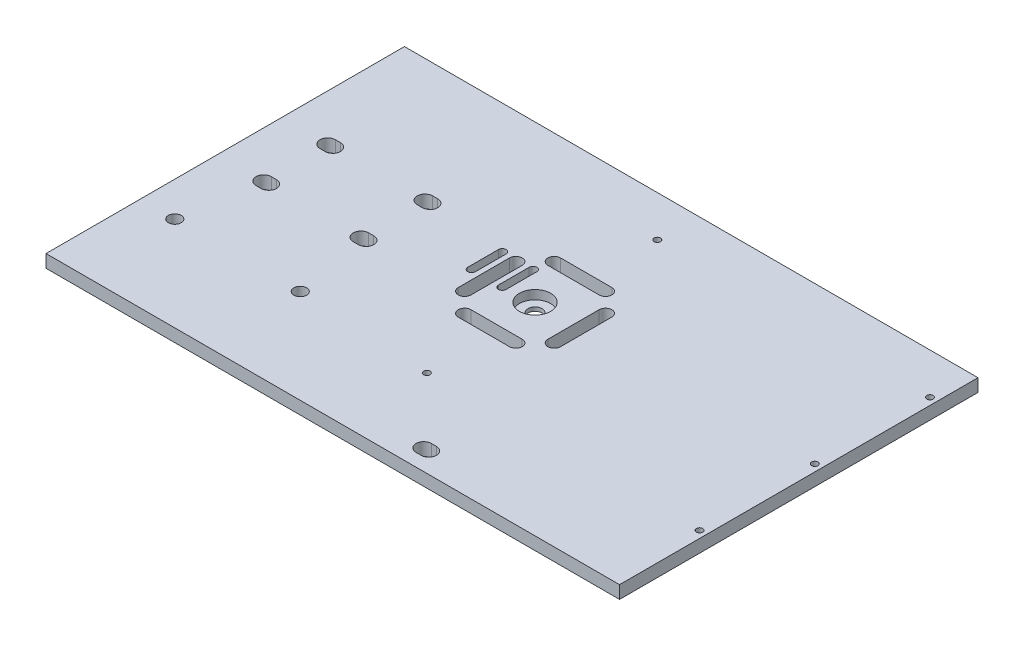
SolidWorks part; units mm, degrees
material "1060 Alloy"
ref_plane "Front Plane" through (0, 0, 0) normal (0, 0, 1) x (1, 0, 0)
ref_plane "Top Plane" through (0, 0, 0) normal (0, 1, 0) x (1, 0, 0)
ref_plane "Right Plane" through (0, 0, 0) normal (1, 0, 0) x (0, 0, -1)
sketch "Sketch1" plane through (0, 0, 0) normal (0, 1, 0) x (1, 0, 0)
  line L1 (-112, -61) -> (112, -61)
  line L2 (-112, -61) -> (-112, 61)
  line L3 (-112, 61) -> (112, 61)
  line L4 (112, -61) -> (112, 61)
  line L5 (-112, -61) -> (112, 61) construction
  line L6 (-112, 61) -> (112, -61) construction
  point P0 (0, 0)
  dimension "D1" = 122
  dimension "D2" = 224
extrude "Boss-Extrude1" add sketch "Sketch1" along normal blind 5
sketch "Sketch2" plane through (0, 0, 0) normal (0, -1, 0) x (1, 0, 0)
  line L0 (-17.5, 10) -> (-17.5, -10) construction
  line L1 (44.2539, 0) -> (-44.2539, 0) construction
  line L2 (-15, 10) -> (-15, -10)
  line L3 (-20, 10) -> (-20, -10)
  line L4 (0, -44.7868) -> (0, 44.7868) construction
  arc A0 (-15, 10) -> (-20, 10) centre (-17.5, 10) ccw
  arc A1 (-20, -10) -> (-15, -10) centre (-17.5, -10) ccw
  point P4 (-17.5, 0)
  dimension "D3" = 2.5
  dimension "D1" = 0
  dimension "D2" = 17.5
  dimension "D4" = 20
extrude "Cut-Extrude1" cut sketch "Sketch2" against normal blind 5
ref_axis "Axis1" through (0, -43.5149, 0) along (0, 1, 0)
pattern_circular "CirPattern1" count 4 over 360 about axis through (0, -43.5149, 0) along (0, 1, 0) of "Cut-Extrude1"
sketch "Sketch3" plane through (0, 0, 0) normal (0, 1, 0) x (1, 0, 0)
  circle A0 centre (0, 0) radius 2.75
  dimension "D1" = 5.5
extrude "Cut-Extrude5" cut sketch "Sketch3" along normal blind 5
hole_wizard "CBORE for M5 Hex Head Bolt1" positions "Sketch4" profile "Sketch6" counterbore size "M5" standard "ISO"
sketch "Sketch4" plane through (0, 5, 0) normal (0, 1, 0) x (1, 0, 0)
  point P0 (0, 0)
sketch "Sketch6" plane through (0, 5, 0) normal (1, 0, 0) x (0, 0, 1)
  line L0 (0, 0) -> (0, 14.0524)
  line L1 (0, 14.0524) -> (2.75, 12.4)
  line L2 (2.75, 12.4) -> (2.75, 3.5)
  line L3 (2.75, 3.5) -> (6.119, 3.5)
  line L4 (6.119, 3.5) -> (6.119, 0)
  line L5 (6.119, 0) -> (0, 0)
  line L10 (0, 14.0524) -> (-2.75, 12.4) construction
  line L11 (0, -6.35) -> (0, 107.95) construction
  dimension "Hole Dia." = 5.5
  dimension "Hole Depth" = 12.4
  dimension "C'Bore Dia." = 12.238
  dimension "C'Bore Depth" = 3.5
  dimension "Drill Angle" = 118
hole_wizard "Ø2.5mm Dowel Hole1" positions "Sketch9" profile "Sketch10" hole size "Ø2.5" standard "ISO"
sketch "Sketch9" plane through (0, 5, 0) normal (0, 1, 0) x (1, 0, 0)
  line L0 (-112, -61) -> (112, -61) construction
  line L1 (112, 61) -> (-112, 61) construction
  line L2 (112, -61) -> (112, 61) construction
  point P0 (109.25, -45)
  point P2 (109.25, 0)
  point P4 (109.25, 45)
  dimension "D1" = 16
  dimension "D2" = 16
  dimension "D3" = 2.75
  dimension "D4" = 0
  dimension "D5" = 0
sketch "Sketch10" plane through (109.25, 5, 45) normal (1, 0, 0) x (0, 0, 1)
  line L0 (0, 0) -> (0, 13.1511)
  line L1 (0, 13.1511) -> (1.25, 12.4)
  line L2 (1.25, 12.4) -> (1.25, 0)
  line L5 (1.25, 0) -> (0, 0)
  line L10 (0, 13.1511) -> (-1.25, 12.4) construction
  line L11 (0, -6.35) -> (0, 107.95) construction
  dimension "Hole Dia." = 2.5
  dimension "Hole Depth" = 12.4
  dimension "Drill Angle" = 118
ref_plane "Plane2" through (2.75, 0, 0) normal (1, 0, 0) x (0, 0, -1)
pattern_linear "LPattern1" count 2 spacing 106.5 along (-1, 0, 0) of "Ø2.5mm Dowel Hole1"
sketch "Sketch11" plane through (0, 1.5, 0) normal (0, 1, 0) x (1, 0, 0)
  circle A0 centre (0, 0) radius 2.75
  circle A1 centre (0, 0) radius 4
extrude "Boss-Extrude3" add sketch "Sketch11" against normal up to surface (1.5 mm away) up to face at (2.75, 0, 43.75)
sketch "Sketch12" plane through (0, 5, 0) normal (0, 1, 0) x (1, 0, 0)
  line L1 (-94, -15) -> (-92, -15)
  line L5 (-56, -15) -> (-54, -15)
  line L7 (-56, -9) -> (-54, -9)
  line L9 (-112, -61) -> (112, -61) construction
  line L11 (-94, -9) -> (-92, -9)
  arc A0 (-94, -9) -> (-94, -15) centre (-94, -12) ccw
  arc A1 (-92, -15) -> (-92, -9) centre (-92, -12) ccw
  arc A2 (-56, -9) -> (-56, -15) centre (-56, -12) ccw
  arc A3 (-54, -15) -> (-54, -9) centre (-54, -12) ccw
  dimension "D1" = 3
  dimension "D4" = 3
  dimension "D6" = 36
  dimension "D2" = 2
  dimension "D3" = 2
  dimension "D5" = 46
extrude "Cut-Extrude6" cut sketch "Sketch12" against normal blind 10
pattern_linear "LPattern2" count 2 spacing 25 along (0, 0, -1) of "Cut-Extrude6"
sketch "Sketch13" plane through (0, 5, 0) normal (0, 1, 0) x (1, 0, 0)
  line L0 (-112, 61) -> (-112, -61) construction
  line L1 (-112, -61) -> (112, -61) construction
  circle A0 centre (-98.5, -42.2) radius 2.5
  circle A1 centre (-49.5, -42.2) radius 2.5
  dimension "D1" = 5
  dimension "D2" = 5
  dimension "D3" = 13.5
  dimension "D4" = 62.5
  dimension "D5" = 18.8
extrude "Cut-Extrude7" cut sketch "Sketch13" against normal blind 10
sketch "Sketch15" plane through (0, 0, 61) normal (0, 0, 1) x (1, 0, 0)
  line L1 (-112, 0) -> (112, 0)
  line L2 (-112, 0) -> (-112, 5)
  line L3 (-112, 5) -> (112, 5)
  line L4 (112, 0) -> (112, 5)
extrude "Boss-Extrude4" add sketch "Sketch15" along normal blind 18
sketch "Sketch14" plane through (0, 5, 0) normal (0, 1, 0) x (1, 0, 0)
  line L1 (29.5, -68) -> (27.5, -68)
  line L3 (29.5, -74) -> (27.5, -74)
  line L5 (112, -79) -> (-112, -79) construction
  arc A0 (27.5, -68) -> (27.5, -74) centre (27.5, -71) ccw
  arc A1 (29.5, -74) -> (29.5, -68) centre (29.5, -71) ccw
  dimension "D1" = 3
  dimension "D2" = 2
  dimension "D4" = 5
extrude "Cut-Extrude8" cut sketch "Sketch14" against normal blind 5
sketch "Sketch16" plane through (0, 5, 0) normal (0, 1, 0) x (1, 0, 0)
  line L2 (-13, 10.7) -> (-13, -1.3)
  line L4 (-10, 10.7) -> (-10, -1.3)
  line L6 (-25, 10.7) -> (-25, -1.3)
  line L8 (-22, 10.7) -> (-22, -1.3)
  line L11 (-15, 10) -> (-15, -10) construction
  line L12 (-20, -10) -> (-20, 10) construction
  arc A0 (-13, 10.7) -> (-10, 10.7) centre (-11.5, 10.7) cw
  arc A1 (-13, -1.3) -> (-10, -1.3) centre (-11.5, -1.3) ccw
  arc A3 (-22, 10.7) -> (-25, 10.7) centre (-23.5, 10.7) ccw
  arc A5 (-25, -1.3) -> (-22, -1.3) centre (-23.5, -1.3) ccw
  dimension "D5" = 1.5
  dimension "D2" = 12
  dimension "D3" = 2
  dimension "D4" = 2
extrude "Cut-Extrude9" cut sketch "Sketch16" against normal blind 10
